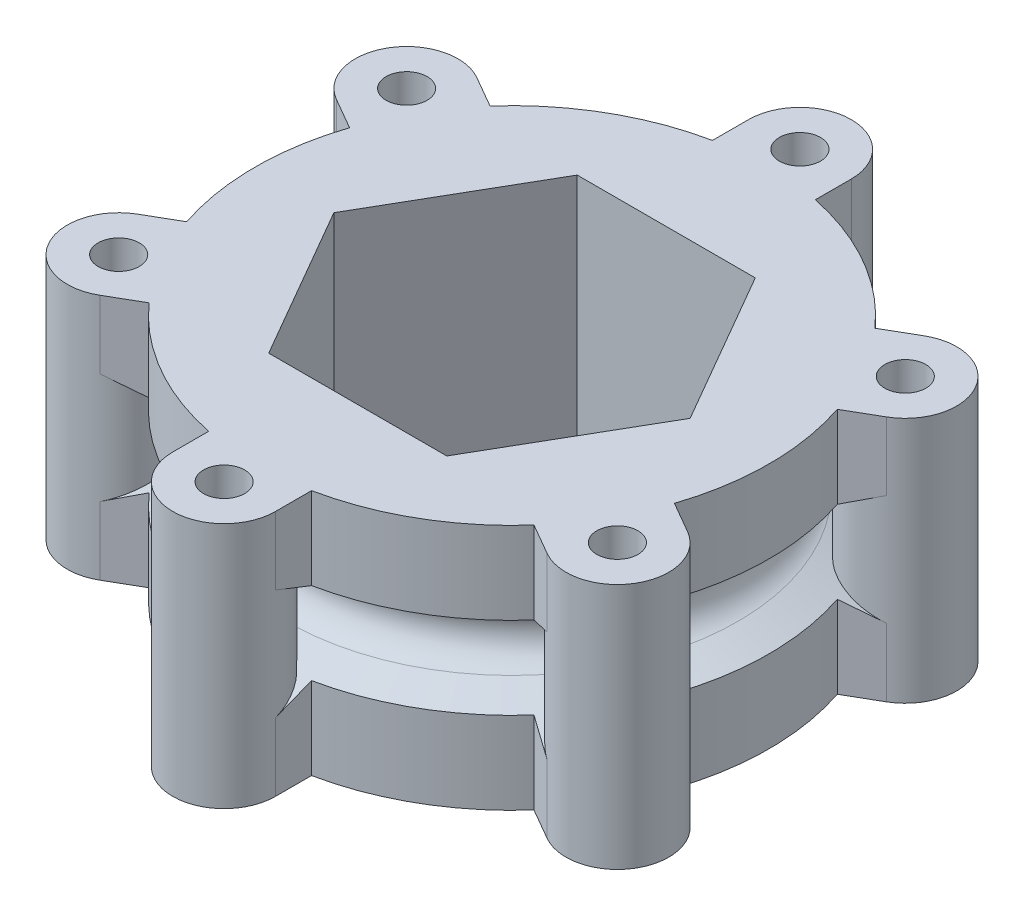
SolidWorks part; units mm, degrees
material "PLA/ABS"
ref_plane "Front Plane" through (0, 0, 0) normal (0, 0, 1) x (1, 0, 0)
ref_plane "Top Plane" through (0, 0, 0) normal (0, 1, 0) x (1, 0, 0)
ref_plane "Right Plane" through (0, 0, 0) normal (1, 0, 0) x (0, 0, -1)
other "Bounding Box"
ref_plane "Default Plane" through (13.8565, 3.175, 6.7999) normal (0, -1, 0) x (-1, 0, 0)
sketch "Sketch1" plane through (0, 0, 0) normal (0, 1, 0) x (1, 0, 0)
  line L0 (17.9605, -17.9605) -> (0, 0) construction
  line L1 (0, 0) -> (17.9605, 17.9605) construction
  line L2 (0, 0) -> (0, 25.4) construction
  circle A0 centre (0, 0) radius 25.4
  point P3 (0, 25.4)
  point P4 (25.4, 0)
  point P5 (-25.4, 0)
  point P6 (0, -25.4)
  point P7 (17.9605, 17.9605)
  point P8 (17.9605, -17.9605)
  dimension "D1" = 50.8
  dimension "D2" = 45
extrude "Boss-Extrude1" add sketch "Sketch1" along normal mid plane 15.24
ref_plane "Plane2" through (-25.4, 0, 0) normal (-1, 0, 0) x (0, 0, 1)
sketch "Sketch9" plane through (-25.4, 0, 0) normal (-1, 0, 0) x (0, 0, 1)
  line L0 (-0.635, -7.62) -> (0.635, -7.62)
  line L1 (-25.4, -7.62) -> (25.4, -7.62) construction
  line L2 (0.635, -7.62) -> (0.635, 0)
  line L3 (25.4, 7.62) -> (-25.4, 7.62) construction
  line L5 (-0.635, 0) -> (-0.635, -7.62)
  line L6 (0.635, -7.62) -> (0, -7.62) construction
  line L7 (0, -7.62) -> (0, 7.62) construction
  line L9 (-0.635, 0) -> (0.635, 0) construction
  line L10 (0.635, 0) -> (0.635, 7.62)
  line L11 (0.635, 7.62) -> (-0.635, 7.62)
  line L13 (-0.635, 7.62) -> (-0.635, 0)
  point P14 (0, 0)
  dimension "D2" = 1.27
extrude "Cut-Extrude4" cut sketch "Sketch9" against normal blind 0.635
sketch "Sketch4" plane through (0, 0, 0) normal (0, 0, 1) x (1, 0, 0)
  line L0 (-25.4, -7.62) -> (-22.225, -7.62)
  line L1 (-25.3921, -7.62) -> (25.4, -7.62) construction
  line L4 (25.4, 7.62) -> (-25.3921, 7.62) construction
  line L5 (-22.225, 7.62) -> (-25.4, 7.62)
  line L6 (-25.4, 7.62) -> (-25.4, -7.62)
  line L7 (-9.525, 0) -> (0, 0) construction
  line L8 (-22.225, -7.62) -> (-22.225, -5.08)
  line L9 (-22.225, -5.08) -> (-13.9469, -1.7687)
  line L10 (-13.9469, 1.7687) -> (-22.225, 5.08)
  line L11 (-22.225, 5.08) -> (-22.225, 7.62)
  arc A0 (-13.9469, 1.7687) -> (-13.9469, -1.7687) centre (-14.6544, 0) cw
  point P17 (-25.4, 0)
  dimension "D4" = 1.905
  dimension "D1" = 3.175
  dimension "D2" = 15.875
  dimension "D3" = 2.54
pattern_circular "CirPattern2" count 20 over 360 about axis through (0, -7.62, 0) along (0, 1, 0) of "Cut-Extrude4"
ref_axis "Axis1" through (0, -9.0805, 0) along (0, 1, 0)
sketch "Sketch3" plane through (0, 7.62, 0) normal (0, 1, 0) x (1, 0, 0)
  line L0 (0, 0) -> (0, 17.78) construction
  line L1 (0, 17.78) -> (0, 25.4) construction
  circle A0 centre (0, 17.78) radius 1.27
  circle A1 centre (0, 0) radius 25.4 construction
  circle A2 centre (0, 17.78) radius 3.175
  dimension "D2" = 2.54
  dimension "D3" = 6.35
  dimension "D1" = 7.62
move or copy body "Body-Move/Copy1" [suppressed] parameters "D1"=0, "D2"=0, "D3"=0
revolve "Cut-Revolve2" cut sketch "Sketch4" angle 360 about axis through (0, -9.0805, 0) along (0, 1, 0)
sketch "Sketch5" plane through (0, 7.62, 0) normal (0, 1, 0) x (1, 0, 0)
  circle A0 centre (0, 17.78) radius 3.175
  circle A1 centre (0, 17.78) radius 1.27 construction
  circle A3 centre (0, 17.78) radius 1.27
  circle A4 centre (0, 17.78) radius 3.175 construction
extrude "Boss-Extrude2" add sketch "Sketch5" against normal through all
sketch "Sketch12" plane through (0, 7.62, 0) normal (0, 1, 0) x (1, 0, 0)
  line L0 (-15.3979, 8.89) -> (0, 0) construction
  line L1 (-15.3979, -8.89) -> (-15.3979, 8.89) construction
  line L2 (-15.3979, 8.89) -> (0, 17.78) construction
  line L3 (-15.3979, -8.89) -> (0, 0) construction
  line L4 (0, 0) -> (0, 17.78) construction
  circle A0 centre (-15.3979, 8.89) radius 3.175
  circle A1 centre (0, 17.78) radius 3.175 construction
  dimension "D3" = 120
extrude "Boss-Extrude6" add sketch "Sketch12" against normal through all
sketch "Sketch17" plane through (0, 0, 0) normal (0, 1, 0) x (1, 0, 0)
  line L0 (0, 17.78) -> (0, 0) construction
  line L1 (0, 0) -> (-15.3979, 8.89) construction
  line L2 (0, 0) -> (-15.3979, -8.89) construction
  line L3 (-18.1476, -10.4775) -> (-19.2474, -11.1125)
  line L4 (0, 20.955) -> (0, 22.225)
  line L5 (-16.9854, -6.1404) -> (-15.0579, -5.0275)
  line L6 (-15.0579, 5.0275) -> (-16.9854, 6.1404)
  line L7 (-13.8104, 11.6396) -> (-11.8829, 10.5268)
  line L8 (-3.175, 17.78) -> (-3.175, 15.5543)
  circle A0 centre (0, 17.78) radius 3.175 construction
  circle A1 centre (-15.3979, 8.89) radius 3.175 construction
  arc A2 (0, 20.955) -> (-3.175, 17.78) centre (0, 17.78) ccw
  arc A3 (-13.8104, 11.6396) -> (-16.9854, 6.1404) centre (-15.3979, 8.89) ccw
  arc A5 (-3.175, 15.5543) -> (-11.8829, 10.5268) centre (0, 0) ccw
  circle A6 centre (0, 17.78) radius 1.27 construction
  arc A7 (-16.9854, -6.1404) -> (-18.1476, -10.4775) centre (-15.3979, -8.89) ccw
  circle A8 centre (0, 0) radius 22.225 construction
  circle A9 centre (0, 17.78) radius 1.27
  circle A10 centre (0, 0) radius 22.225 construction
  arc A11 (0, 22.225) -> (-19.2474, -11.1125) centre (0, 0) ccw
  arc A12 (-15.0579, 5.0275) -> (-15.0579, -5.0275) centre (0, 0) ccw
  circle A13 centre (-15.3979, 8.89) radius 1.27
  circle A15 centre (-15.3979, -8.89) radius 1.27
  dimension "D1" = 6.35
extrude "Cut-Extrude5" cut sketch "Sketch17" against normal through all both and the other way through all
pattern_circular "CirPattern1" count 3 over 360 about axis through (0, 5.08, 0) along (0, -1, 0) of "Boss-Extrude2", "Boss-Extrude6", "Cut-Extrude5"
sketch "Sketch24" plane through (0, -7.62, 0) normal (0, -1, 0) x (1, 0, 0)
  line L1 (5.4993, -9.525) -> (10.9985, 0)
  line L2 (10.9985, 0) -> (5.4993, 9.525)
  line L3 (5.4993, 9.525) -> (-5.4993, 9.525)
  line L4 (-5.4993, 9.525) -> (-10.9985, 0)
  line L5 (-10.9985, 0) -> (-5.4993, -9.525)
  line L6 (-5.4993, -9.525) -> (5.4993, -9.525)
  circle A0 centre (0, 0) radius 6.35 construction
  circle A1 centre (0, 0) radius 9.525 construction
  dimension "D1" = 12.7
  dimension "D2" = 19.05
extrude "Cut-Extrude7" cut sketch "Sketch24" against normal through all
sketch "Sketch33" plane through (0, -7.62, 0) normal (0, -1, 0) x (1, 0, 0)
  line L1 (-6.35, -6.35) -> (6.35, -6.35) construction
  line L2 (-6.35, -6.35) -> (-6.35, 6.35) construction
  line L3 (-6.35, 6.35) -> (6.35, 6.35) construction
  line L4 (6.35, -6.35) -> (6.35, 6.35) construction
  line L5 (-6.35, -6.35) -> (6.35, 6.35) construction
  line L6 (-6.35, 6.35) -> (6.35, -6.35) construction
  circle A0 centre (-6.35, 6.35) radius 2.4892
  circle A1 centre (6.35, 6.35) radius 2.4892
  circle A2 centre (6.35, -6.35) radius 2.4892
  circle A3 centre (-6.35, -6.35) radius 2.4892
  point P0 (0, 0)
  dimension "D1" = 4.9784
  dimension "D2" = 12.7
extrude "Cut-Extrude8" [suppressed] cut sketch "Sketch33" against normal through all
combine bodies "Combine3" [suppressed] bodies to combine 116 167
delete or keep bodies "Body-Delete/Keep 4" [suppressed] bodies 194
sketch "Sketch7" [suppressed] plane through (0, -8.255, 0) normal (0, -1, 0) x (1, 0, 0)
  circle A0 centre (0, 0) radius 44.45
  circle A1 centre (0, 0) radius 38.1 construction
  dimension "D1" = 6.35
extrude "Boss-Extrude4" [suppressed] add sketch "Sketch7" against normal offset from surface (19.685 mm away) 3.175 separate body up to face at (0, 7.62, 0) offset beyond the face yes
combine bodies "Combine2" [suppressed] operation type add bodies to combine 110 114
sketch "Sketch15" [suppressed] plane through (0, 0, 0) normal (1, 0, 0) x (0, 0, -1)
  line L0 (-38.1, -8.255) -> (-43.18, -13.335)
  line L1 (-43.18, -13.335) -> (-36.83, -13.335)
  line L2 (-36.83, -13.335) -> (-31.75, -8.255)
  line L3 (-31.75, -8.255) -> (-38.1, -8.255)
  dimension "D1" = 5.08
  dimension "D2" = 45
  dimension "D3" = 6.35
ref_axis "Axis2" [suppressed] through (0, -9.0805, 0) along (0, 1, 0)
revolve "Revolve1" [suppressed] add sketch "Sketch15" angle 360 about axis through (0, -9.0805, 0) along (0, 1, 0)
fillet "Fillet4" [suppressed] radius 6.35
sketch "Sketch27" [suppressed] plane through (0, 11.43, 0) normal (0, 1, 0) x (1, 0, 0)
  line L0 (37.5671, 6.35) -> (44.45, 6.35)
  line L1 (44.45, -6.35) -> (37.5671, -6.35)
  line L2 (38.1, 0) -> (44.45, 0) construction
  circle A0 centre (44.45, 0) radius 1.905
  arc A1 (37.5671, -6.35) -> (37.5671, 6.35) centre (0, 0) ccw
  circle A2 centre (0, 0) radius 38.1 construction
  arc A3 (44.45, 6.35) -> (44.45, -6.35) centre (44.45, 0) cw
  dimension "D2" = 3.81
  dimension "D3" = 6.35
  dimension "D1" = 6.35
extrude "Boss-Extrude13" [suppressed] add sketch "Sketch27" against normal blind 9.525
pattern_circular "CirPattern7" [suppressed] count 3 over 360 of bodies 177
split "Split1" [suppressed] bodies to split 124
sketch "Sketch19" [suppressed] plane through (0, 11.43, 0) normal (0, 1, 0) x (1, 0, 0)
  line L0 (-20.447, 35.4152) -> (-19.177, 33.2155)
  line L1 (-20.447, -35.4152) -> (-19.177, -33.2155)
  line L2 (-40.894, 0) -> (0, 0) construction
  arc A0 (-19.177, 33.2155) -> (-19.177, -33.2155) centre (0, 0) ccw
  circle A1 centre (0, 0) radius 38.1 construction
  arc A2 (-20.447, 35.4152) -> (-20.447, -35.4152) centre (0, 0) ccw
  dimension "D2" = 2.54
  dimension "D3" = 0.254
  dimension "D1" = 120
extrude "Boss-Extrude10" [suppressed] add sketch "Sketch19" against normal blind 6.35 separate body
sketch "Sketch21" [suppressed] plane through (0, 11.43, 0) normal (0, 1, 0) x (1, 0, 0)
  line L0 (-19.177, 33.2155) -> (-19.05, 32.9956)
  line L1 (-19.177, -33.2155) -> (-19.05, -32.9956)
  line L2 (-19.177, 33.2155) -> (-20.447, 35.4152) construction
  line L3 (-20.447, -35.4152) -> (-19.177, -33.2155) construction
  arc A1 (-19.177, 33.2155) -> (-19.177, -33.2155) centre (0, 0) ccw construction
  arc A2 (-19.05, 32.9956) -> (-19.05, -32.9956) centre (0, 0) ccw
  arc A3 (-19.177, 33.2155) -> (-19.177, -33.2155) centre (0, 0) ccw
  circle A4 centre (0, 0) radius 38.1 construction
extrude "Boss-Extrude11" [suppressed] add sketch "Sketch21" against normal blind 3.1496
pattern_circular "CirPattern6" [suppressed] count 3 over 360 reverse direction yes of bodies 137 132
combine bodies "Combine4" [suppressed] bodies to combine 137 137 135 134
chamfer "Chamfer4" [suppressed] distance 0.635 angle 45
delete or keep bodies "Body-Delete/Keep 1" [suppressed] type delete bodies bodies 133
delete or keep bodies "Body-Delete/Keep 2" [suppressed] type delete bodies bodies 121
mirror "Mirror1" [suppressed] about plane through (0, 0, 0) normal (1, 0, 0) of bodies 121
delete or keep bodies "Body-Delete/Keep 3" [suppressed] type delete bodies bodies 121
sketch "Sketch28" [suppressed] plane through (0, 8.255, 0) normal (0, -1, 0) x (1, 0, 0)
  circle A0 centre (0, 0) radius 15.24
  dimension "D1" = 30.48
extrude "Boss-Extrude14" [suppressed] add sketch "Sketch28" along normal blind 0.635
sketch "Sketch29" [suppressed] plane through (0, 7.62, 0) normal (0, -1, 0) x (1, 0, 0)
  circle A0 centre (0, 0) radius 9.144
  dimension "D1" = 18.288
extrude "Boss-Extrude15" [suppressed] add sketch "Sketch29" along normal blind 10.16
sketch "Sketch30" [suppressed] plane through (0, -7.62, 0) normal (0, -1, 0) x (1, 0, 0)
  circle A12 centre (0, 0) radius 24.13
  circle A13 centre (0, 0) radius 21.59
  circle A14 centre (0, 0) radius 25.4 construction
  dimension "D1" = 1.27
  dimension "D2" = 2.54
extrude "Boss-Extrude16" [suppressed] add sketch "Sketch30" along normal blind 1.6002 separate body
sketch "Sketch31" [suppressed] plane through (0, -9.2202, 0) normal (0, -1, 0) x (1, 0, 0)
  line L0 (-5.9055, 17.78) -> (-5.9055, 23.3962)
  line L1 (-5.9055, 23.3962) -> (5.9055, 23.3962)
  line L2 (5.9055, 23.3962) -> (5.9055, 17.78)
  line L3 (0, 0) -> (0, 17.78) construction
  line L4 (-1.5875, 12.0919) -> (1.5875, 12.0919) construction
  line L5 (-1.5875, 12.0919) -> (-1.5875, 7.62)
  line L6 (-1.5875, 7.62) -> (1.5875, 7.62)
  line L7 (1.5875, 12.0919) -> (1.5875, 7.62)
  line L8 (-1.5875, 12.0919) -> (1.5875, 7.62) construction
  line L9 (-1.5875, 7.62) -> (1.5875, 12.0919) construction
  arc A0 (-1.5875, 12.0919) -> (-5.9055, 17.78) centre (0, 17.78) cw
  circle A1 centre (0, 17.78) radius 2.7305
  arc A2 (5.9055, 17.78) -> (1.5875, 12.0919) centre (0, 17.78) cw
  circle A3 centre (0, 17.78) radius 1.27 construction
  circle A4 centre (0, 0) radius 24.13 construction
  point P0 (0, 9.8559)
  dimension "D1" = 3.175
  dimension "D2" = 5.461
  dimension "D3" = 7.62
  dimension "D4" = 3.175
extrude "Boss-Extrude17" [suppressed] add sketch "Sketch31" against normal up to surface (1.6002 mm away) up to face at (0, -7.62, 0)
fillet "Fillet6" [suppressed] radius 2.54
pattern_circular "CirPattern8" [suppressed] count 6 over 360 of bodies 182
sketch "Sketch32" [suppressed] plane through (0, -9.2202, 0) normal (0, -1, 0) x (1, 0, 0)
  line L0 (0, 0) -> (-1.8604, 26.605) construction
  line L1 (1.8604, 26.605) -> (0.1905, 24.1292)
  line L2 (0, 0) -> (0, 26.67) construction
  line L3 (-1.4167, 24.0884) -> (-1.8604, 26.605)
  line L4 (-1.8604, 26.605) -> (-0.1905, 24.1292)
  line L5 (-0.1905, 24.1292) -> (-1.4167, 24.0884)
  line L6 (1.4167, 24.0884) -> (1.8604, 26.605)
  line L7 (0.1905, 24.1292) -> (1.4167, 24.0884)
  circle A0 centre (0, 0) radius 24.13 construction
  circle A1 centre (0, 0) radius 26.67 construction
  circle A2 centre (0, 0) radius 25.4 construction
  dimension "D2" = 1.27
  dimension "D1" = 6
  dimension "D3" = 30
  dimension "D4" = 4
extrude "Boss-Extrude18" [suppressed] add sketch "Sketch32" against normal up to surface (1.6002 mm away) up to face at (0, -7.62, 0)
fillet "Fillet7" [suppressed] radius 0.635
pattern_circular "CirPattern9" [suppressed] count 10 over 360 of bodies 184
delete or keep bodies "Body-Delete/Keep 5" [suppressed] bodies 185
sketch "Sketch34" [suppressed] plane through (0, -9.2202, 0) normal (0, -1, 0) x (1, 0, 0)
  circle A0 centre (0, 0) radius 6.4135
  circle A1 centre (0, 0) radius 9.525
  dimension "D1" = 12.827
  dimension "D2" = 19.05
extrude "Boss-Extrude19" [suppressed] add sketch "Sketch34" against normal up to surface (1.6002 mm away) up to face at (0, -7.62, 0)
